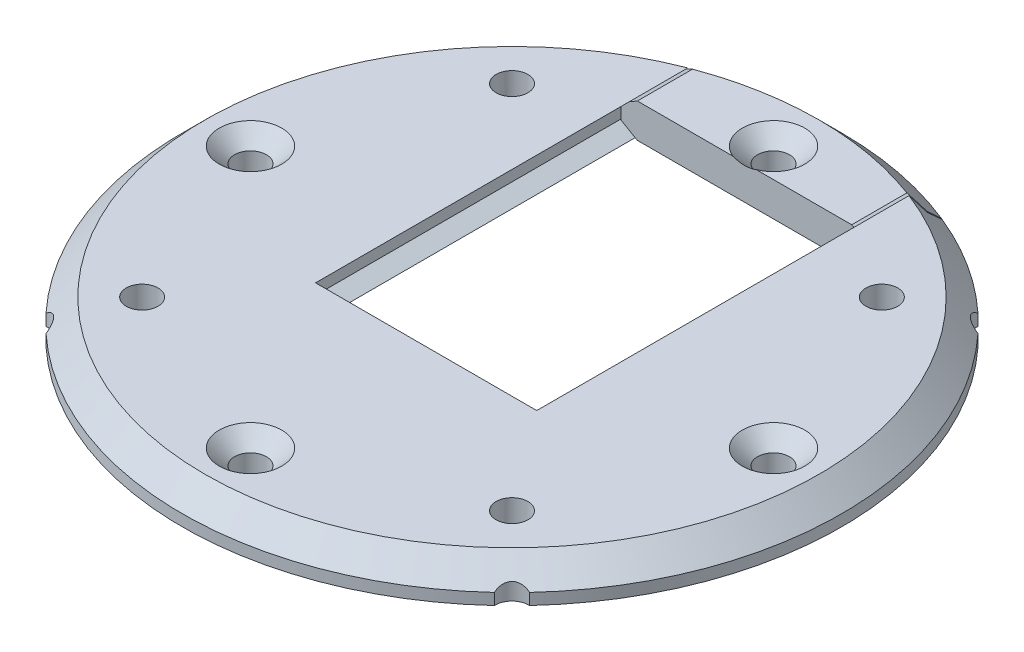
SolidWorks part; units mm, degrees
ref_plane "Front Plane" through (0, 0, 0) normal (0, 0, 1) x (1, 0, 0)
ref_plane "Top Plane" through (0, 0, 0) normal (0, 1, 0) x (1, 0, 0)
ref_plane "Right Plane" through (0, 0, 0) normal (1, 0, 0) x (0, 0, -1)
sketch "Sketch1" plane through (0, 0, 0) normal (0, 1, 0) x (1, 0, 0)
  circle A0 centre (0, 0) radius 29
  dimension "D1" = 58
extrude "Boss-Extrude1" add sketch "Sketch1" along normal mid plane 3
sketch "Sketch2" plane through (0, 1.5, 0) normal (0, 1, 0) x (1, 0, 0)
  line L0 (-11.025, 7.55) -> (-11.025, 29)
  line L1 (-11.025, -7.55) -> (11.025, -7.55)
  line L2 (-11.025, -7.55) -> (-11.025, 7.55)
  line L3 (-11.025, 7.55) -> (11.025, 7.55) construction
  line L4 (11.025, -7.55) -> (11.025, 7.55)
  line L5 (-11.025, -7.55) -> (11.025, 7.55) construction
  line L6 (-11.025, 7.55) -> (11.025, -7.55) construction
  line L7 (-11.025, 29) -> (11.025, 29)
  line L8 (11.025, 29) -> (11.025, 7.55)
  circle A0 centre (0, 0) radius 29 construction
  point P0 (0, 0)
  dimension "D1" = 7.55
  dimension "D2" = 22.05
extrude "Cut-Extrude1" cut sketch "Sketch2" against normal through all
sketch "Sketch3" plane through (0, 0, 7.55) normal (0, 0, -1) x (-1, 0, 0)
  line L0 (0, -1.5) -> (0, 1.5) construction
  line L1 (11.025, -1.5) -> (-11.025, -1.5) construction
  line L2 (11.025, 1.5) -> (-11.025, 1.5) construction
  line L3 (-11.525, -1.5) -> (-9.726, -1.5)
  line L5 (-9.726, -1.5) -> (-11.025, -0.75)
  line L6 (-11.025, -1.5) -> (-11.025, 1.5) construction
  line L7 (-11.025, -0.75) -> (-11.025, 0.75)
  line L8 (-11.025, 0.75) -> (-9.726, 1.5)
  line L9 (-9.726, 1.5) -> (-11.525, 1.5)
  line L10 (29, 1.5) -> (-29, 1.5) construction
  line L11 (-11.525, 1.5) -> (-11.525, -1.5)
  line L12 (-29, -1.5) -> (29, -1.5) construction
  line L13 (-11.025, -1.5) -> (-11.025, 1.5) construction
  line L21 (11.525, 1.5) -> (11.525, -1.5)
  line L22 (9.726, 1.5) -> (11.525, 1.5)
  line L23 (11.025, 0.75) -> (9.726, 1.5)
  line L24 (11.025, -0.75) -> (11.025, 0.75)
  line L25 (9.726, -1.5) -> (11.025, -0.75)
  line L26 (11.525, -1.5) -> (9.726, -1.5)
  point P10 (-11.025, 0)
  dimension "D1" = 0.5
  dimension "D2" = 60
  dimension "D3" = 1.5
extrude "Boss-Extrude2" add sketch "Sketch3" along normal up to surface (34.1615 mm away) up to face at (0, 0, 1.0887)
ref_plane "Plane1" through (0, 0, -20.45) normal (0, 0, -1) x (-1, 0, 0)
sketch "Sketch6" plane through (0, 0, -20.45) normal (0, 0, -1) x (-1, 0, 0)
  line L0 (-9.726, -1.5) -> (-11.025, -0.75) construction
  line L1 (-11.025, -0.75) -> (-11.025, 0.75) construction
  line L2 (-11.025, 0.75) -> (-9.726, 1.5) construction
  line L3 (-9.726, -1.5) -> (-11.025, -0.75) construction
  line L4 (-11.025, -0.75) -> (-11.025, 0.75) construction
  line L5 (-11.025, 0.75) -> (-9.726, 1.5) construction
  line L6 (-9.426, 1.5) -> (-10.875, 0.6634)
  line L7 (9.726, 1.5) -> (-9.726, 1.5) construction
  line L8 (-10.875, 0.6634) -> (-10.875, -0.6634)
  line L9 (-10.875, -0.6634) -> (-9.426, -1.5)
  line L10 (9.726, -1.5) -> (-9.726, -1.5) construction
  line L11 (0, 0) -> (0, 1.5) construction
  line L12 (10.875, -0.6634) -> (9.426, -1.5)
  line L13 (10.875, 0.6634) -> (10.875, -0.6634)
  line L14 (9.426, 1.5) -> (10.875, 0.6634)
  line L15 (-10.875, 0.6634) -> (-10.95, 0.7933) construction
  line L16 (-10.875, 0.6634) -> (-11.025, 0.6634) construction
  line L17 (10.875, -0.6634) -> (9.426, -1.5)
  line L18 (10.875, 0.6634) -> (10.875, -0.6634)
  line L19 (9.426, 1.5) -> (10.875, 0.6634)
  line L20 (-9.426, 1.5) -> (9.426, 1.5)
  line L21 (9.426, -1.5) -> (-9.426, -1.5)
  dimension "D1" = 0.15
extrude "Boss-Extrude3" add sketch "Sketch6" along normal up to surface (6.4337 mm away) separate body contours L21 L12 L13 L14 L20 L6 L8 L9 region at (0, 0, -20.45) up to face at (0, 0, -12.9953)
chamfer "Chamfer1" distance 2 angle 45 1 edges at (0, 1.5, 29)
chamfer "Chamfer2" distance 2 angle 45 2 edges at (-4.7783, 1.5, -28.6036) (4.7783, 1.5, -28.6036)
sketch "Sketch5" plane through (0, 1.5, 0) normal (0, 1, 0) x (1, 0, 0)
  circle A0 centre (0, 0) radius 23 construction
  circle A1 centre (0, 23) radius 1.4
  circle A2 centre (16.2635, 16.2635) radius 1.4
  circle A3 centre (23, 0) radius 1.4
  circle A4 centre (16.2635, -16.2635) radius 1.4
  circle A5 centre (0, -23) radius 1.4
  circle A6 centre (-16.2635, -16.2635) radius 1.4
  circle A7 centre (-23, 0) radius 1.4
  circle A8 centre (-16.2635, 16.2635) radius 1.4
  point P21 (0, 0)
  dimension "D1" = 46
  dimension "D2" = 2.8
  dimension "D3" = 8
extrude "Cut-Extrude2" cut sketch "Sketch5" against normal through all
hole_wizard "CSK for M2.5 Flat Head Machine Screw1" positions "Sketch7" profile "Sketch8" countersink size "M2.5" standard "ANSI Metric" end condition through all
sketch "Sketch7" plane through (0, 1.5, 0) normal (0, 1, 0) x (1, 0, 0)
  circle A0 centre (0, 23) radius 1.125 construction
  point P13 (0, 23)
  point P16 (23, 0)
  point P19 (0, -23)
  point P22 (-23, 0)
  point P26 (0, 0)
  point P27 (0, 0)
sketch "Sketch8" plane through (0, 1.5, -23) normal (1, 0, 0) x (0, 0, 1)
  line L0 (0, 0) -> (0, 3)
  line L1 (0, 3) -> (1.35, 3)
  line L2 (1.35, 3) -> (1.35, 1.4)
  line L3 (1.35, 1.4) -> (2.75, 0)
  line L5 (2.75, 0) -> (0, 0)
  line L6 (-1.35, 1.4) -> (-2.75, 0) construction
  line L11 (0, -6.35) -> (0, 107.95) construction
  dimension "Thru Hole Dia." = 2.7
  dimension "Thru Hole Depth" = 3
  dimension "Near C'Sink Dia." = 5.5
  dimension "Near C'Sink Angle" = 90
sketch "Sketch10" [suppressed] plane through (0, 1.5, 0) normal (0, 1, 0) x (1, 0, 0)
  line L0 (0, 0) -> (0, -30) construction
  line L1 (15, -12.5) -> (11.5, -12.5) construction
  line L6 (-15, 12.5) -> (-11.5, 12.5) construction
  line L7 (-15, 12.5) -> (-15, -12.5) construction
  line L8 (-15, -12.5) -> (-11.5, -12.5) construction
  line L9 (-11.5, 12.5) -> (-11.5, -12.5) construction
  line L10 (-11.5, -12.5) -> (11.5, -12.5) construction
  line L11 (-11.5, -12.5) -> (-11.5, -9) construction
  line L12 (-11.5, -9) -> (11.5, -9) construction
  line L13 (11.5, -12.5) -> (11.5, -9) construction
  line L14 (11.5, 12.5) -> (11.5, -12.5) construction
  line L15 (15, 12.5) -> (11.5, 12.5) construction
  line L16 (15, 12.5) -> (15, -12.5) construction
  line L17 (0, 0) -> (-11.5, 0) construction
  line L18 (-11.5, -9) -> (-11.5, 12.5)
  line L19 (-11.5, 12.5) -> (-15, 12.5)
  line L20 (-15, 12.5) -> (-15, -12.5)
  line L21 (-15, -12.5) -> (15, -12.5)
  line L22 (15, -12.5) -> (15, 12.5)
  line L23 (15, 12.5) -> (11.5, 12.5)
  line L24 (11.5, 12.5) -> (11.5, -9)
  line L25 (11.5, -9) -> (-11.5, -9)
  arc A0 (-11.025, 27.9007) -> (11.025, 27.9007) centre (0, 0) ccw construction
  point P18 (-11.5, 0)
  point P36 (0, -12.5)
  point P37 (0, -9)
  dimension "D5" = 30
  dimension "D1" = 3.5
  dimension "D2" = 3.5
  dimension "D3" = 23
  dimension "D4" = 25
  dimension "D6" = 25
extrude "Boss-Extrude4" [suppressed] add sketch "Sketch10" along normal blind 5
sketch "Sketch11" [suppressed] plane through (0, 0, 9) normal (0, 0, -1) x (-1, 0, 0)
  line L0 (-11.5, 6.5) -> (11.5, 6.5) construction
  line L1 (0, 6.5) -> (-2.45, 5.0855) construction
  line L2 (-2.45, 5.0855) -> (-2.45, 2.2565)
  line L3 (-2.45, 2.2565) -> (0, 0.842)
  line L4 (0, 0.842) -> (2.45, 2.2565)
  line L5 (2.45, 2.2565) -> (2.45, 5.0855)
  line L6 (2.45, 5.0855) -> (0, 6.5) construction
  line L7 (-2.45, 5.0855) -> (-2.45, 6.5)
  line L8 (-2.45, 6.5) -> (2.45, 6.5)
  line L9 (2.45, 6.5) -> (2.45, 5.0855)
  circle A0 centre (0, 3.671) radius 2.45 construction
  dimension "D1" = 4.9
extrude "Cut-Extrude3" [suppressed] cut sketch "Sketch11" against normal blind 2
chamfer "Chamfer3" [suppressed] distance 3.5 angle 45
sketch "Sketch12" [suppressed] plane through (-11.5, 0, 0) normal (1, 0, 0) x (0, 0, -1)
  line L0 (0, 0) -> (0, 6.5) construction
  line L1 (-9, 6.5) -> (9, 6.5) construction
  line L2 (-9, 5.0855) -> (-9, 6.5)
  line L3 (-6.55, 6.5) -> (-9, 5.0855) construction
  line L4 (-9, 5.0855) -> (-9, 2.2565)
  line L5 (-9, 2.2565) -> (-6.55, 0.842)
  line L6 (-6.55, 0.842) -> (-4.1, 2.2565)
  line L7 (-4.1, 2.2565) -> (-4.1, 5.0855)
  line L8 (-4.1, 5.0855) -> (-6.55, 6.5) construction
  line L9 (-9, 6.5) -> (-4.1, 6.5)
  line L10 (-4.1, 6.5) -> (-4.1, 5.0855)
  line L11 (9, 6.5) -> (4.1, 6.5)
  line L12 (9, 5.0855) -> (9, 6.5)
  line L13 (9, 5.0855) -> (9, 2.2565)
  line L14 (9, 2.2565) -> (6.55, 0.842)
  line L15 (6.55, 0.842) -> (4.1, 2.2565)
  line L16 (4.1, 2.2565) -> (4.1, 5.0855)
  line L17 (4.1, 6.5) -> (4.1, 5.0855)
  line L18 (-9, 6.5) -> (-9, 1.5) construction
  circle A0 centre (-6.55, 3.671) radius 2.45 construction
  dimension "D2" = 4.9
extrude "Cut-Extrude4" [suppressed] cut sketch "Sketch12" against normal blind 2
mirror "Mirror1" [suppressed] about plane through (0, 0, 0) normal (1, 0, 0)
sketch "Sketch13" [suppressed] plane through (0, 0, 11) normal (0, 0, -1) x (-1, 0, 0)
  circle A0 centre (0, 3.671) radius 1.4
  dimension "D1" = 2.8
extrude "Cut-Extrude5" [suppressed] cut sketch "Sketch13" against normal blind 2
sketch "Sketch14" [suppressed] plane through (-15, 0, 0) normal (-1, 0, 0) x (0, 0, 1)
  line L0 (0, 6.5) -> (0, 0) construction
  line L1 (-9, 6.5) -> (9, 6.5) construction
  circle A0 centre (6.55, 3.671) radius 1.4
  circle A1 centre (-6.55, 3.671) radius 1.4
  dimension "D1" = 2.8
extrude "Cut-Extrude6" [suppressed] cut sketch "Sketch14" against normal through all both and the other way through all
sketch "Sketch15" plane through (0, 0, 0) normal (0, 1, 0) x (1, 0, 0)
  line L0 (0, 0) -> (-20.5061, 20.5061) construction
  line L1 (0, 0) -> (0, -29) construction
  arc A0 (-11.025, 26.8226) -> (11.025, 26.8226) centre (0, 0) ccw construction
  circle A1 centre (-21.2132, 21.2132) radius 1.5
  circle A2 centre (21.2132, 21.2132) radius 1.5
  circle A3 centre (21.2132, -21.2132) radius 1.5
  circle A4 centre (-21.2132, -21.2132) radius 1.5
  point P17 (0, 0)
  dimension "D2" = 3
  dimension "D1" = 135
  dimension "D3" = 1
  dimension "D4" = 4
extrude "Cut-Extrude7" cut sketch "Sketch15" against normal through all
equation "\"m2.5 width\"= 4.9mm"
equation "\"D1@Sketch11\"=\"m2.5 width\""
equation "\"D2@Sketch12\"=\"m2.5 width\""
